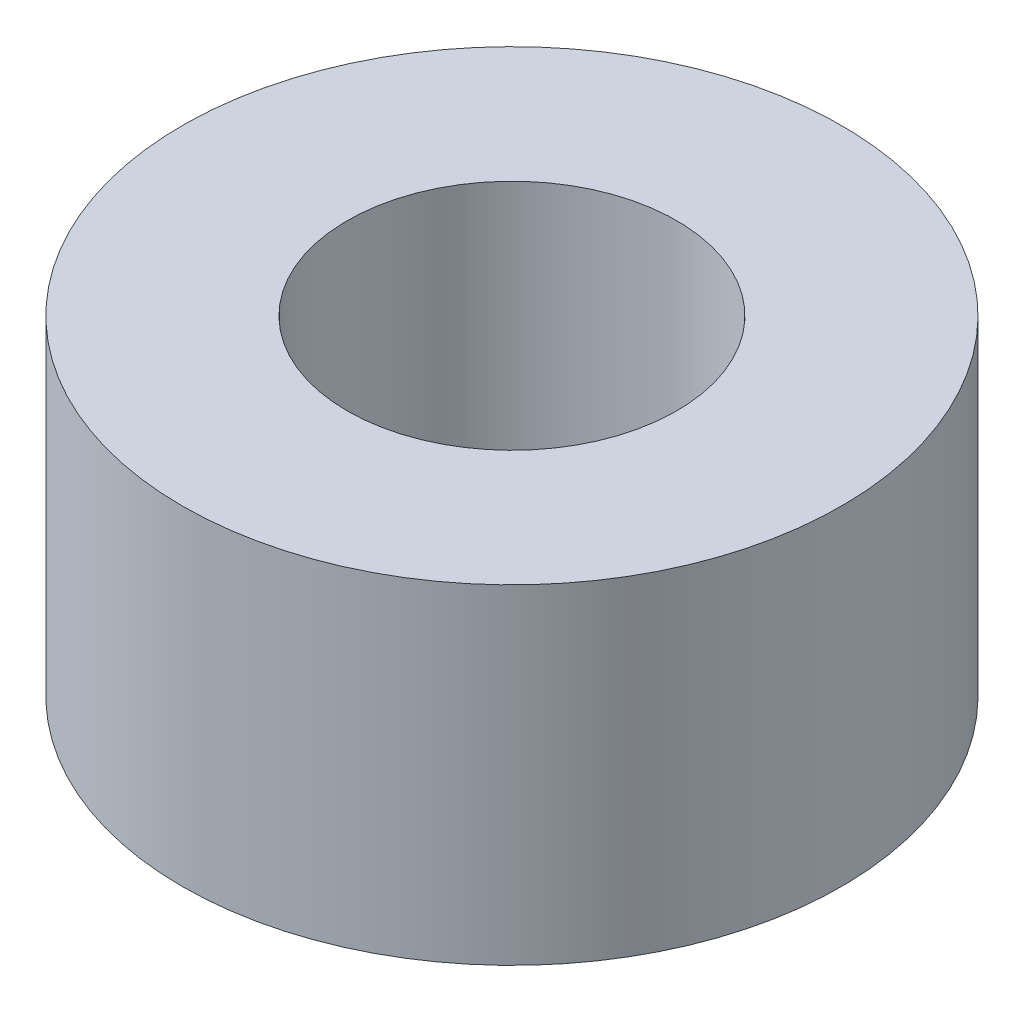
SolidWorks part; units mm, degrees
ref_plane "Front" through (0, 0, 0) normal (0, 0, 1) x (1, 0, 0)
ref_plane "Top" through (0, 0, 0) normal (0, 1, 0) x (1, 0, 0)
ref_plane "Right" through (0, 0, 0) normal (1, 0, 0) x (0, 0, -1)
ref_axis "side-side" through (80.9, 0, 0) along (-1, 0, 0)
ref_axis "up-down" through (0, 50, 0) along (0, -1, 0)
ref_axis "front-back" through (0, 0, -80.9) along (0, 0, 1)
sketch "Sketch1" plane through (0, 0, 0) normal (0, 1, 0) x (1, 0, 0)
  circle A0 centre (0, 0) radius 6.35
  circle A1 centre (0, 0) radius 3.175
  dimension "D1" = 6.35
  dimension "D2" = 12.7
extrude "Boss-Extrude1" add sketch "Sketch1" along normal mid plane 6.35
